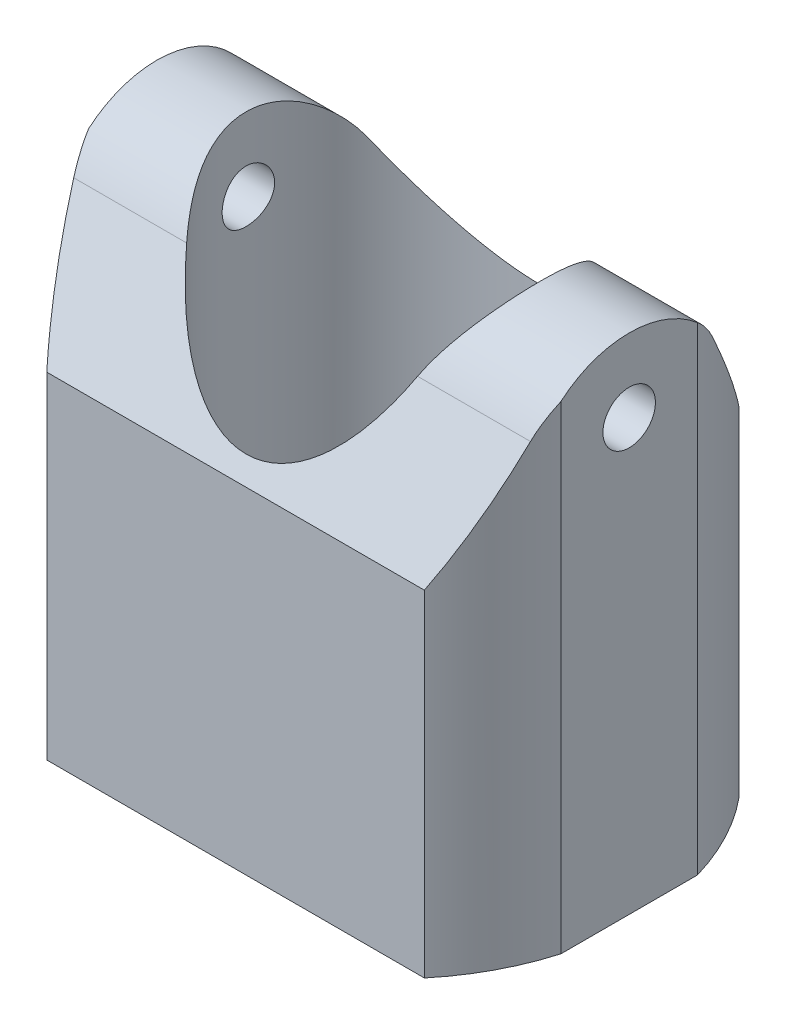
SolidWorks part; units mm, degrees
ref_plane "Front Plane" through (0, 0, 0) normal (0, 0, 1) x (1, 0, 0)
ref_plane "Top Plane" through (0, 0, 0) normal (0, 1, 0) x (1, 0, 0)
ref_plane "Right Plane" through (0, 0, 0) normal (1, 0, 0) x (0, 0, -1)
sketch "Sketch1" plane through (0, 0, 0) normal (0, 1, 0) x (1, 0, 0)
  line L0 (-22.5, -15) -> (22.5, -15)
  line L7 (-22.5, -15) -> (-22.5, 15)
  line L8 (-22.5, 15) -> (22.5, 15)
  line L9 (22.5, -15) -> (22.5, 15)
  line L10 (-22.5, -15) -> (22.5, 15) construction
  line L11 (-22.5, 15) -> (22.5, -15) construction
  line L12 (-15.5, -9) -> (15.5, -9) construction
  line L13 (-15.5, -9) -> (-15.5, 9) construction
  line L14 (-15.5, 9) -> (15.5, 9) construction
  line L15 (15.5, -9) -> (15.5, 9) construction
  line L16 (-15.5, -9) -> (15.5, 9) construction
  line L17 (-15.5, 9) -> (15.5, -9) construction
  circle A2 centre (0, 0) radius 14
  circle A3 centre (-15.5, 9) radius 2.5
  circle A4 centre (15.5, 9) radius 2.5
  circle A5 centre (15.5, -9) radius 2.5
  circle A6 centre (-15.5, -9) radius 2.5
  circle A7 centre (0, 0) radius 23.4201
  point P8 (0, 0)
  point P24 (22.5, 6.5)
  point P25 (22.5, -6.5)
  dimension "D1" = 28
  dimension "D8" = 5
  dimension "D4" = 30
  dimension "D5" = 45
  dimension "D6" = 31
  dimension "D7" = 18
  dimension "D9" = 13
extrude "Boss-Extrude1" add sketch "Sketch1" along normal blind 32 contours L0 A7 L9 L8 L7 A6 A5 A4 A3 A2 region at (-20.2067, 0, 10.7307)
ref_plane "Plane1" through (22.5, 0, 0) normal (1, 0, 0) x (0, 0, -1)
sketch "Sketch3" plane through (22.5, 0, 0) normal (1, 0, 0) x (0, 0, -1)
  line L0 (-15, 32) -> (15, 32)
  line L1 (15, 32) -> (15, 0) construction
  line L2 (15, 32) -> (0, 57.9808)
  line L3 (0, 57.9808) -> (-15, 32)
extrude "Boss-Extrude2" add sketch "Sketch3" against normal blind 45
sketch "Sketch4" plane through (0, 0, 0) normal (0, -1, 0) x (1, 0, 0)
  circle A0 centre (0, 0) radius 23.4201
  circle A1 centre (0, 0) radius 49.3971
  circle A2 centre (0, 0) radius 14
  circle M7 centre (0, 0) radius 14
  arc M9 (-17.9861, 15) -> (-22.5, 6.5) centre (0, 0) ccw
  arc M11 (-22.5, -6.5) -> (-17.9861, -15) centre (0, 0) ccw
  arc M13 (17.9861, -15) -> (22.5, -6.5) centre (0, 0) ccw
  arc M15 (22.5, 6.5) -> (17.9861, 15) centre (0, 0) ccw
extrude "Cut-Extrude1" cut sketch "Sketch4" against normal blind 90 contours M7 | A1 A0 M13 M11 M9 M15 region at (-47.9999, 0, 0) region at (0, 0, 0)
fillet "Fillet1" radius 10 2 edges at (-18.25, 57.9808, 0) (18.25, 57.9808, 0)
sketch "Sketch6" plane through (-22.5, 0, 0) normal (-1, 0, 0) x (0, 0, 1)
  circle A0 centre (0, 41) radius 2.5
  dimension "D1" = 5
  dimension "D2" = 41
extrude "Cut-Extrude2" cut sketch "Sketch6" against normal blind 90
